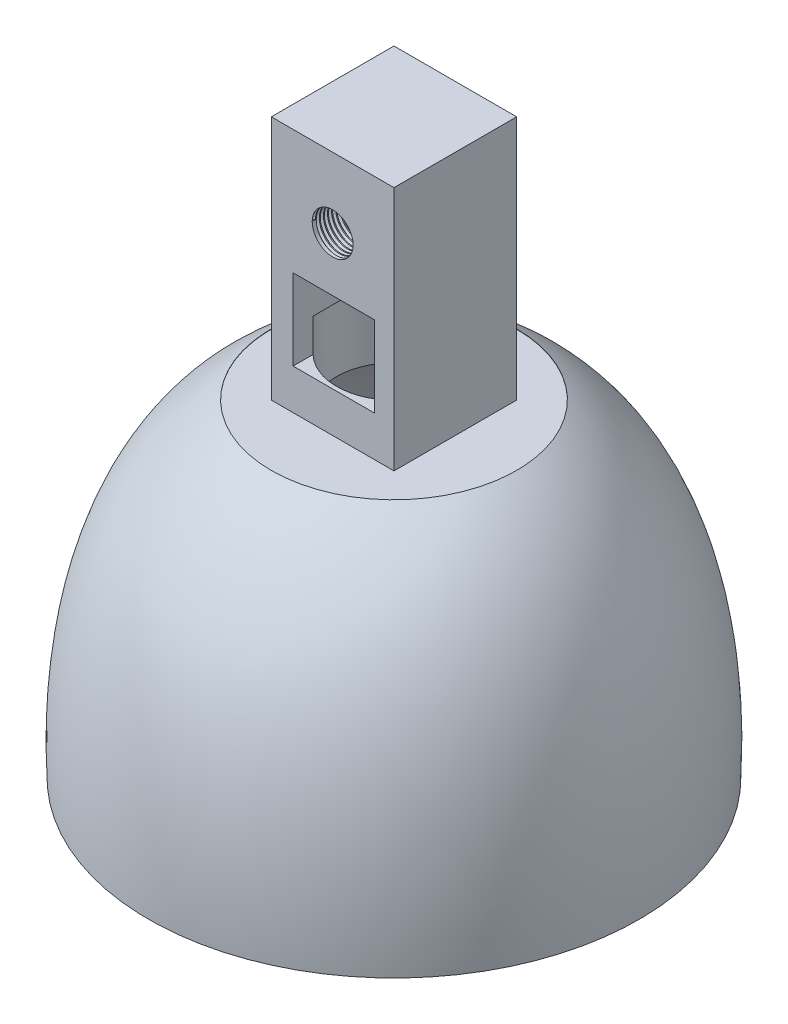
SolidWorks part; units mm, degrees
ref_plane "Front Plane" through (0, 0, 0) normal (0, 0, 1) x (1, 0, 0)
ref_plane "Top Plane" through (0, 0, 0) normal (0, 1, 0) x (1, 0, 0)
ref_plane "Right Plane" through (0, 0, 0) normal (1, 0, 0) x (0, 0, -1)
sketch "Sketch2" plane through (0, 0, 0) normal (0, 0, 1) x (1, 0, 0)
  line L0 (0, 0) -> (0, 101.6) construction
  line L1 (0, 0) -> (0, 101.6)
  line L2 (0, 101.6) -> (38.1, 101.6)
  line L3 (38.1, 101.6) -> (38.1, 101.7149)
  line L12 (0, 0) -> (76.2, 0)
  spline S0 degree 3 poles (38.1, 101.7149) (71.0328, 80.7706) (77.8572, 35.356) (76.2, 0) knots 0 0 0 0 1 1 1 1
  dimension "D1" = 101.6
  dimension "D2" = 38.1
  dimension "D3" = 76.2
revolve "Revolve1" add sketch "Sketch2" angle 360 about L0
shell "Shell1" thickness 2.54
sketch "Sketch5" plane through (0, 101.6, 0) normal (0, 1, 0) x (1, 0, 0)
  line L5 (-19.05, -19.05) -> (19.05, -19.05)
  line L6 (-19.05, -19.05) -> (-19.05, 19.05)
  line L7 (-19.05, 19.05) -> (19.05, 19.05)
  line L8 (19.05, -19.05) -> (19.05, 19.05)
extrude "Boss-Extrude2" add sketch "Sketch5" along normal blind 76.2 contours L6 L5 L8 L7
sketch "Sketch6" plane through (0, 0, -19.05) normal (0, 0, -1) x (-1, 0, 0)
  circle A0 centre (0, 155.9845) radius 6.35
  dimension "D1" = 12.7
extrude "Cut-Extrude2" cut sketch "Sketch6" against normal blind 76.2
thread "Thread2" pitch 1.27 start angle 0, offset 0, length 0, pitch 1.27, diameter 12.7
ref_plane "Plane2" through (-6.35, 155.9845, 19.05) normal (0, -1, 0) x (-1, 0, 0)
sketch "Thread Profile2" plane through (-6.35, 155.9845, 19.05) normal (0, -1, 0) x (-1, 0, 0)
  line L0 (0, 0) -> (0, 1.27) construction
  line L1 (0, 0) -> (0.6874, 0.3969)
  line L2 (0.6874, 0.3969) -> (0.6874, 0.5556)
  line L3 (0.6874, 0.5556) -> (0, 0.9525)
  line L4 (0.6874, 0.4762) -> (0, 0.4762) construction
  line L11 (0, 0) -> (0, 0.9525)
  point P2 (0, 0)
  dimension "Pitch" = 1.27
  dimension "Profile_Angle" = 60
  dimension "Profile_Land" = 0.1588
  dimension "Profile_Height" = 0.6874
sketch "Sketch11" plane through (0, 99.06, 0) normal (0, -1, 0) x (1, 0, 0)
  circle A0 centre (0, 0) radius 17.78
  dimension "D1" = 35.56
extrude "Cut-Extrude5" cut sketch "Sketch11" against normal blind 25.4
sketch "Sketch12" plane through (0, 0, 19.05) normal (0, 0, 1) x (1, 0, 0)
  line L1 (-12.2948, 139.218) -> (12.9436, 139.218)
  line L2 (-12.2948, 139.218) -> (-12.2948, 114.129)
  line L3 (-12.2948, 114.129) -> (12.9436, 114.129)
  line L4 (12.9436, 139.218) -> (12.9436, 114.129)
extrude "Cut-Extrude6" cut sketch "Sketch12" against normal through all
